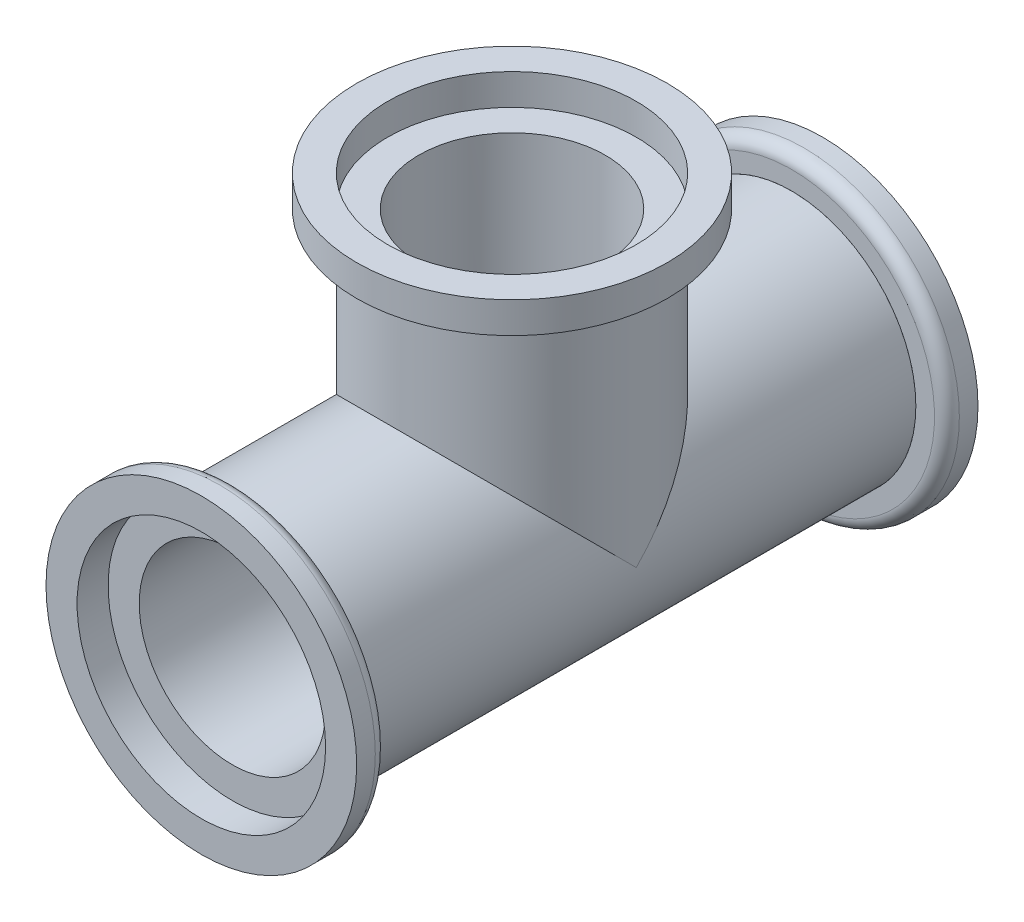
SolidWorks part; units mm, degrees
ref_plane "Alzado" through (0, 0, 0) normal (0, 0, 1) x (1, 0, 0)
ref_plane "Planta" through (0, 0, 0) normal (0, 1, 0) x (1, 0, 0)
ref_plane "Vista lateral" through (0, 0, 0) normal (1, 0, 0) x (0, 0, -1)
sketch "Croquis2" plane through (0, 0, 0) normal (0, 0, 1) x (1, 0, 0)
  circle A0 centre (0, 0) radius 7.5
  circle A1 centre (0, 0) radius 10
  dimension "D1" = 15
  dimension "D2" = 20
extrude "Saliente-Extruir1" add sketch "Croquis2" along normal blind 22.5 and the other way blind 22.5
sketch "Croquis3" plane through (0, 0, 22.5) normal (0, 0, 1) x (1, 0, 0)
  circle A0 centre (0, 0) radius 12.5
  circle A1 centre (0, 0) radius 10
  dimension "D1" = 25
extrude "Saliente-Extruir2" add sketch "Croquis3" along normal blind 2.5 separate body
fillet "Redondeo1" radius 1 1 edges at (12.5, 0, 22.5)
sketch "Croquis4" plane through (0, 0, -22.5) normal (0, 0, -1) x (-1, 0, 0)
  circle A0 centre (0, 0) radius 12.5
  circle A1 centre (0, 0) radius 10
  dimension "D1" = 25
extrude "Saliente-Extruir3" add sketch "Croquis4" along normal blind 2.5 separate body
fillet "Redondeo2" radius 1 1 edges at (-12.5, 0, -22.5)
ref_plane "Plano1" through (0, 20, 0) normal (0, 1, 0) x (1, 0, 0)
sketch "Croquis5" plane through (0, 20, 0) normal (0, 1, 0) x (1, 0, 0)
  circle A1 centre (0, 0) radius 10
  circle A2 centre (0, 0) radius 7.5
  dimension "D1" = 15
  dimension "D2" = 20
extrude "Saliente-Extruir4" add sketch "Croquis5" against normal up to next
sketch "Croquis7" plane through (0, 20, 0) normal (0, 1, 0) x (1, 0, 0)
  circle A0 centre (0, 0) radius 12.5
  circle A1 centre (0, 0) radius 10
  dimension "D1" = 25
extrude "Saliente-Extruir5" add sketch "Croquis7" along normal blind 2.5 separate body
sketch "Croquis8" plane through (0, 20, 0) normal (0, 1, 0) x (1, 0, 0)
  circle A0 centre (0, 0) radius 7.5
extrude "Cortar-Extruir4" cut sketch "Croquis8" against normal blind 18.5
